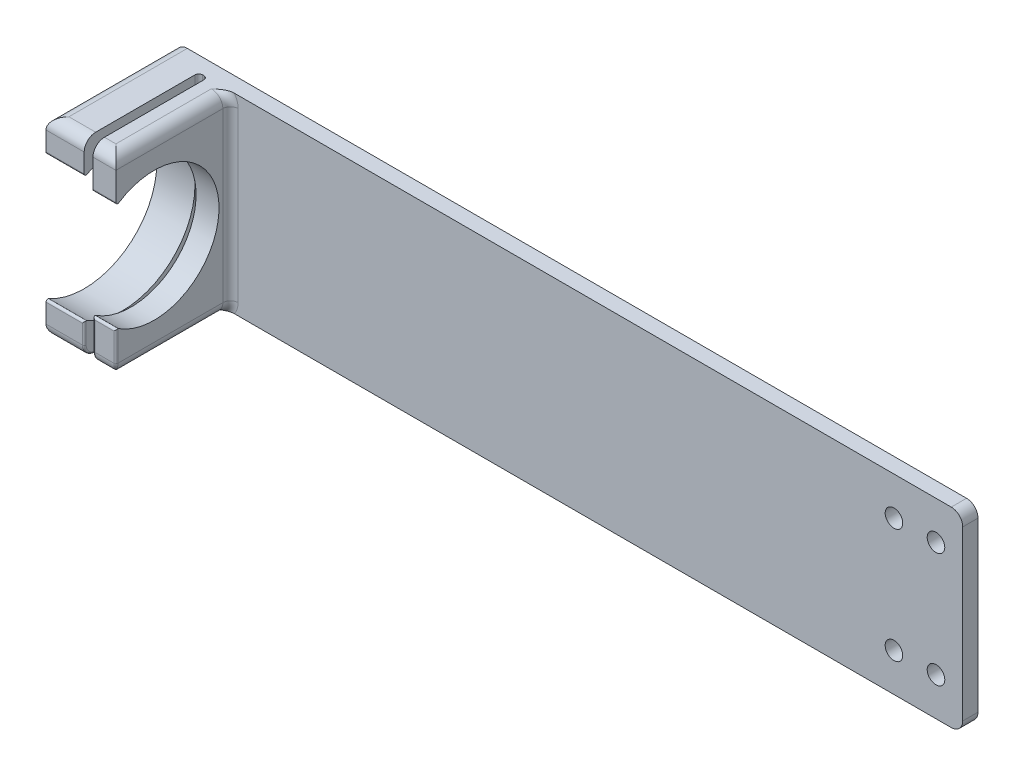
SolidWorks part; units mm, degrees
ref_plane "正面" through (0, 0, 0) normal (0, 0, 1) x (1, 0, 0)
ref_plane "平面" through (0, 0, 0) normal (0, 1, 0) x (1, 0, 0)
ref_plane "右側面" through (0, 0, 0) normal (1, 0, 0) x (0, 0, -1)
sketch "ｽｹｯﾁ1" plane through (0, 0, 0) normal (0, 0, 1) x (1, 0, 0)
  line L1 (0, 0) -> (-210, 0)
  line L2 (0, 0) -> (0, 50)
  line L3 (0, 50) -> (-210, 50)
  line L4 (-210, 0) -> (-210, 50)
  dimension "D1" = 50
  dimension "D2" = 210
extrude "ﾎﾞｽ - 押し出し1" add sketch "ｽｹｯﾁ1" along normal blind 4
sketch "ｽｹｯﾁ4" plane through (0, 0, 4) normal (0, 0, 1) x (1, 0, 0)
  line L0 (-210, 25) -> (0, 25) construction
  line L1 (-210, 50) -> (-210, 0) construction
  line L2 (0, 0) -> (0, 50) construction
  circle A0 centre (-7, 40) radius 2.3
  circle A1 centre (-18, 40) radius 2.3
  circle A2 centre (-7, 10) radius 2.3
  circle A3 centre (-18, 10) radius 2.3
  dimension "D1" = 4.6
  dimension "D2" = 4.6
  dimension "D3" = 4.6
  dimension "D4" = 4.6
  dimension "D5" = 7
  dimension "D6" = 7
  dimension "D7" = 30
  dimension "D8" = 15
  dimension "D9" = 11
  dimension "D10" = 11
  dimension "D11" = 30
  dimension "D12" = 15
extrude "ｶｯﾄ - 押し出し1" cut sketch "ｽｹｯﾁ4" against normal up to next and the other way through all
sketch "ｽｹｯﾁ5" plane through (-210, 0, 0) normal (-1, 0, 0) x (0, 0, 1)
  line L0 (4, 50) -> (4, 0) construction
  line L2 (4, 50) -> (34, 50)
  line L3 (4, 50) -> (4, 0)
  line L4 (4, 0) -> (34, 0)
  line L5 (34, 50) -> (34, 0)
  circle A0 centre (24, 25) radius 19
  line M6 (4, 0) -> (4, 50)
  dimension "D1" = 38
  dimension "D2" = 20
  dimension "D3" = 30
  dimension "D4" = 25
  dimension "D5" = 50
extrude "ﾎﾞｽ - 押し出し2" add sketch "ｽｹｯﾁ5" against normal blind 10 contours A0 L5 L2 L4 M6 region at (-210, 49.4169, 19)
ref_plane "平面1" through (-197.7, 0, 0) normal (1, 0, 0) x (0, 0, -1)
sketch "ｽｹｯﾁ6" plane through (-197.7, 0, 0) normal (1, 0, 0) x (0, 0, -1)
  line L0 (-4, 0) -> (-4, 50) construction
  line L1 (-4, 0) -> (-34, 0) construction
  line L2 (-4, 0) -> (-4, 50) construction
  line L3 (-34, 50) -> (-4, 50)
  line L4 (-34, 50) -> (-34, 0)
  line L5 (-34, 0) -> (-4, 0)
  line L6 (-4, 50) -> (-4, 0)
  line L7 (-34, 50) -> (-34, 41.1555) construction
  line L8 (-34, 50) -> (0, 50) construction
  circle A0 centre (-24, 25) radius 17
  dimension "D1" = 34
  dimension "D2" = 20
  dimension "D3" = 25
extrude "ﾎﾞｽ - 押し出し3" add sketch "ｽｹｯﾁ6" along normal blind 6 contours A0 L4 L5 L6 L3 region at (-197.7, 49.4169, 19)
fillet "ﾌｨﾚｯﾄ1" radius 3 10 edges at (-191.7, 0, 19) (-191.7, 50, 19) (-210, 0, 17) (-210, 50, 17) (-205, 0, 34) (-194.7, 0, 34) (-205, 50, 34) (-194.7, 50, 34) (0, 0, 2) (0, 50, 2)
fillet "ﾌｨﾚｯﾄ2" radius 2 3 edges at (-192.5787, 49.1213, 4) (-192.5787, 0.8787, 4) (-191.7, 25, 4)
fillet "ﾌｨﾚｯﾄ3" radius 1 2 edges at (-200, 25, 4) (-197.7, 25, 4)
fillet "ﾌｨﾚｯﾄ4" radius 0.5 15 edges at (-192.5787, 0.8787, 33.1213) (-200, 5.9223, 34) (-200, 0.8787, 33.1213) (-200, 0, 18) (-199.7071, 0, 4.2929) (-198.85, 0, 4) (-197.9929, 0, 4.2929) (-197.7, 0, 18) (-197.7, 0.8787, 33.1213) (-194.7, 11.2523, 34) (-191.7, 7.1261, 34) (-197.7, 7.1261, 34) (-205, 41.1555, 34) (-194.7, 38.7477, 34) (-205, 8.8445, 34)
